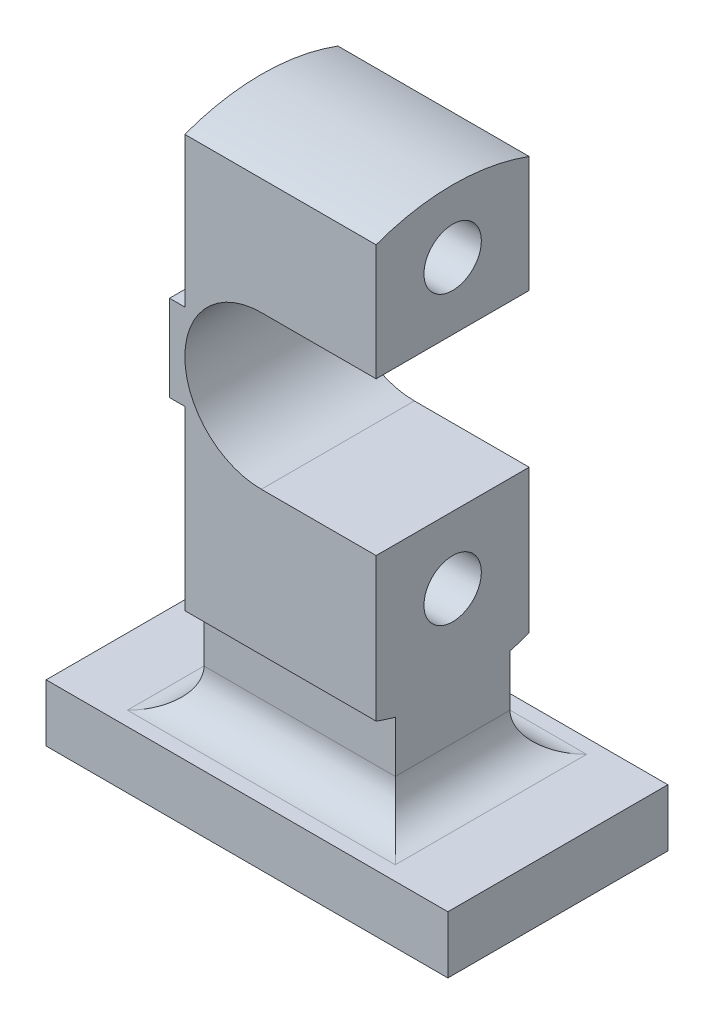
SolidWorks part; units mm, degrees
ref_plane "Front Plane" through (0, 0, 0) normal (0, 0, 1) x (1, 0, 0)
ref_plane "Top Plane" through (0, 0, 0) normal (0, 1, 0) x (1, 0, 0)
ref_plane "Right Plane" through (0, 0, 0) normal (1, 0, 0) x (0, 0, -1)
sketch "Sketch1" plane through (0, 0, 0) normal (0, 1, 0) x (1, 0, 0)
  line L1 (-105, 57.5) -> (105, 57.5)
  line L2 (-105, 57.5) -> (-105, -57.5)
  line L3 (-105, -57.5) -> (105, -57.5)
  line L4 (105, 57.5) -> (105, -57.5)
  line L5 (-105, 57.5) -> (105, -57.5) construction
  line L6 (-105, -57.5) -> (105, 57.5) construction
  point P0 (0, 0)
  dimension "D1" = 210
  dimension "D2" = 115
extrude "Boss-Extrude2" add sketch "Sketch1" along normal blind 30
ref_plane "Plane1" through (0, 0, 0) normal (1, 0, 0) x (0, 0, -1)
sketch "Sketch6" plane through (0, 0, 0) normal (1, 0, 0) x (0, 0, -1)
  line L5 (30, 25.3292) -> (-30, 25.3292)
  line L6 (30, 25.3292) -> (30, 85.3292)
  line L7 (30, 85.3292) -> (-30, 85.3292)
  line L8 (-30, 25.3292) -> (-30, 85.3292)
  dimension "D1" = 60
  dimension "D2" = 60
  dimension "D3" = 30
  dimension "D4" = 30
extrude "Boss-Extrude3" add sketch "Sketch6" along normal mid plane 100
ref_plane "Plane2" through (0, 0, 0) normal (1, 0, 0) x (0, 0, -1)
sketch "Sketch8" plane through (0, 0, 0) normal (1, 0, 0) x (0, 0, -1)
  line L0 (0, 82.8608) -> (0, 187.8608) construction
  line L1 (40, 295.6801) -> (40, 80.0415)
  line L2 (-40, 295.6801) -> (-40, 80.0415)
  line L3 (57.5, 30) -> (-57.5, 30) construction
  arc A0 (-40, 80.0415) -> (40, 80.0415) centre (0, 187.8608) ccw
  arc A1 (40, 295.6801) -> (-40, 295.6801) centre (0, 187.8608) ccw
  circle A2 centre (0, 270) radius 15
  circle A3 centre (0, 120) radius 15
  dimension "D2" = 230
  dimension "D6" = 30
  dimension "D7" = 30
  dimension "D1" = 105
  dimension "D3" = 40
  dimension "D4" = 90
  dimension "D5" = 150
extrude "Boss-Extrude4" add sketch "Sketch8" along normal mid plane 100
fillet "Fillet1" radius 20 4 edges at (-50, 30, 0) (0, 30, -30) (50, 30, 0) (0, 30, 30)
sketch "Sketch9" plane through (0, 0, -40) normal (0, 0, -1) x (-1, 0, 0)
  line L0 (10, 369.137) -> (10, 102.9462) construction
  line L1 (-179.7911, 195) -> (151.3732, 195) construction
  line L2 (-105, 0) -> (105, 0) construction
  line L3 (50, 80.0415) -> (50, 295.6801) construction
  line L4 (10, 235) -> (-50, 235)
  line L6 (-50, 80.0415) -> (-50, 295.6801) construction
  line L7 (10, 155) -> (-50, 155)
  line L8 (50, 217.5) -> (58, 217.5)
  line L9 (50, 217.5) -> (50, 172.5)
  line L10 (50, 172.5) -> (58, 172.5)
  line L11 (58, 217.5) -> (58, 172.5)
  arc A0 (10, 155) -> (10, 235) centre (10, 195) ccw
  line M8 (50, 80.0415) -> (50, 295.6801)
  line M10 (-50, 295.6801) -> (-50, 80.0415)
  dimension "D2" = 80
  dimension "D1" = 40
  dimension "D3" = 195
  dimension "D4" = 8
  dimension "D5" = 22.5
  dimension "D6" = 22.5
  dimension "D7" = 45
extrude "Boss-Extrude5" add sketch "Sketch9" against normal blind 80 contours L11 L8 L9 L10 M8 region at (-54, 195, -40)
extrude "Cut-Extrude1" cut sketch "Sketch9<3>" against normal through all contours L7 A0 L4 M10 region at (3.8561, 195, -40)
sketch "Sketch9<3>" plane through (0, 0, -40) normal (0, 0, -1) x (-1, 0, 0) same geometry as "Sketch9"
